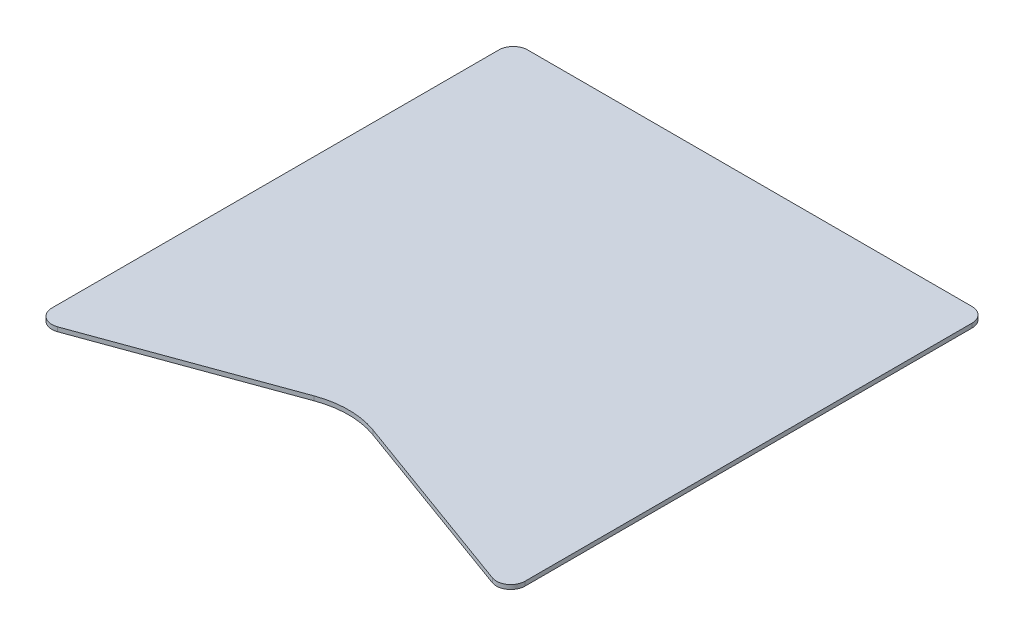
SolidWorks part; units mm, degrees
ref_plane "Front Plane" through (0, 0, 0) normal (0, 0, 1) x (1, 0, 0)
ref_plane "Top Plane" through (0, 0, 0) normal (0, 1, 0) x (1, 0, 0)
ref_plane "Right Plane" through (0, 0, 0) normal (1, 0, 0) x (0, 0, -1)
sketch "Sketch3" plane through (0, 0, 0) normal (0, 1, 0) x (1, 0, 0)
  line L0 (165, 0) -> (998.6493, -303.4235)
  line L1 (0, 0) -> (330, 0)
  line L2 (0, 0) -> (0, 330)
  line L3 (0, 330) -> (330, 330)
  line L4 (330, 0) -> (330, 330)
  line L5 (0, 0) -> (330, 0)
  line L6 (0, 0) -> (0, -60.0551)
  line L7 (0, -60.0551) -> (330, -60.0551)
  line L8 (330, 0) -> (330, -60.0551)
  line L9 (165, 0) -> (-668.6493, -303.4235)
  line L10 (-668.6493, -319.3862) -> (165, -15.9627)
  line L11 (165, -15.9627) -> (998.6493, -319.3862)
  line L12 (-523.6468, -250.6469) -> (0, 0)
  line L13 (-668.6493, -303.4235) -> (0, 16.6298)
  line L14 (15, 0) -> (15, 315)
  line L15 (15, 315) -> (315, 315)
  line L16 (315, 0) -> (315, 315)
  line L17 (0, -25.0551) -> (330, -25.0551)
  line L18 (15, -10.0551) -> (315, -10.0551)
  line L19 (315, -10.0551) -> (315, 0)
  line L20 (15, 0) -> (15, -10.0551)
  line L21 (165, 330) -> (165, 0) construction
  line L22 (998.6493, -303.4235) -> (330, 16.6298)
  line L23 (853.6468, -250.6469) -> (330, 0)
  line L24 (15, 15) -> (315, 15)
  line L25 (-25, 32.3797) -> (15, 32.3797)
  line L26 (-25, 32.3797) -> (-7.7302, -3.7001)
  line L27 (-50, -51.6492) -> (-67.2698, -15.5693)
  line L28 (-50, -51.6492) -> (-36.3192, -89.2369)
  line L29 (165, -79.8133) -> (139.3485, -9.3364)
  line L30 (165, -79.8133) -> (190.6515, -9.3364)
  line L31 (0, 40) -> (15, 40) construction
  line L32 (-23.9741, 5.1545) -> (-17.4979, -8.3755) construction
  line L33 (127.6952, -13.5778) -> (132.8255, -27.6732) construction
  circle A0 centre (-50, -51.6492) radius 40
  circle A1 centre (-50, -51.6492) radius 25
  circle A2 centre (165, -79.8133) radius 75
  circle A3 centre (165, -79.8133) radius 60
  circle A4 centre (380, -51.6492) radius 25
  circle A5 centre (380, -51.6492) radius 40
  circle A6 centre (-25, 32.3797) radius 40
  circle A7 centre (-25, 32.3797) radius 25
  circle A8 centre (355, 32.3797) radius 25
  circle A9 centre (355, 32.3797) radius 40
  dimension "D5" = 150
  dimension "D10" = 80
  dimension "D13" = 80
  dimension "D1" = 330
  dimension "D2" = 330
  dimension "D3" = 15
  dimension "D4" = 15
  dimension "D7" = 15
  dimension "D8" = 35
  dimension "D9" = 70
  dimension "D11" = 50
  dimension "D12" = 15
  dimension "D14" = 290
  dimension "D15" = 48
  dimension "D16" = 180
  dimension "D6" = 15
extrude "Boss-Extrude1" add sketch "Sketch3" along normal blind 3 contours L14 L24 L16 L15 | L16 A9 L4 L3 L2 A6 L14 L15 | L25 A6 L2 | L2 A6 L25 | L26 A6 L2 L13 | L13 A6 L26 | A6 L13 A0 L12 | L12 A0 L27 | L27 A0 L12 | A1 L12 A0 L9 | L9 A0 L28 | L28 A0 L9 | A1 L9 A0 L12 | A0 L9 L6 L12 | A0 L10 L7 L9 | L17 L6 L9 | L20 L1 L6 L17 L9 L18 | A6 L2 L1 L14 | L24 L14 L5 L1 L16 | L5 L20 L18 L9 | A2 L17 L9 L7 L10 | L17 A2 L10 | A2 L18 L9 L17 | L18 A2 L17 L10 L29 | L11 L30 L18 L29 L10 | L29 A2 L18 | L30 A2 L29 L18 | A2 L0 L9 | L18 L19 L1 L0 | A3 L11 L10 | L17 A2 L18 L30 L11 | L11 A2 L17 | A2 L17 L0 L18 | L18 A2 L30 | L19 L18 L0 L17 L8 L5 | A2 L18 L0 | A2 L9 L18 | A6 L12 L2 | A2 L11 L7 L0 L17 | L17 L0 L8 | L11 A5 L0 L7 | L0 A5 L23 L8 | A5 L0 | A5 L23 A4 L0 | A4 | A5 L0 A4 L23 | A5 L23 | L22 A9 L23 A5 | A9 L22 L4 | L4 A9 L16 L5 | L23 A9 L4 | A9 L4 | L22 A8 L4 | A7 L13 L2 | A1 region at (246.673, 0, 4.8576) region at (83.327, 0, 4.8576) region at (165, 0, -7.5) region at (165, 0, 3.8141) region at (191.2006, 0, 9.8141) region at (165, 0, 7.9368) region at (192.103, 0, 9.8735) region at (54.9076, 0, 16.1557) region at (10.3469, 0, -7.7626) region at (319.6531, 0, -7.7626) region at (275.0924, 0, 16.1557) region at (137.897, 0, 9.8735) region at (138.7994, 0, 9.8141) region at (216.3603, 0, 20.7054) region at (165, 0, 15.032) region at (198.1809, 0, 19.4214) region at (-1.8939, 0, 0.5645) region at (-9.3638, 0, 27.8405) region at (165, 0, -165) region at (339.3638, 0, 27.8405) region at (331.8939, 0, 0.5645) region at (113.6397, 0, 20.7054) region at (131.8191, 0, 19.4214) region at (297.9461, 0, 36.7218) region at (266.6993, 0, 44.3391) region at (165, 0, 19.0139) region at (211.7215, 0, 29.7189) region at (-5.7034, 0, -6.5438) region at (6.1083, 0, -20.3096) region at (32.0539, 0, 36.7218) region at (-22.4563, 0, 0.891) region at (-37.5, 0, 9.6347) region at (11.4561, 0, -49.8927) region at (6.1083, 0, -44.4498) region at (323.8917, 0, -32.3797) region at (346.5095, 0, -1.7482) region at (367.5, 0, 9.6347) region at (63.3007, 0, 44.3391) region at (118.2785, 0, 29.7189) region at (326.6299, 0, 68.8353) region at (-3.0031, 0, -18.5218) region at (3.3701, 0, 68.8353) region at (-24.7924, 0, 41.0585) region at (-52.5437, 0, 18.3784) region at (333.0031, 0, -18.5218) region at (393.4309, 0, 23.5896) region at (354.7924, 0, 41.0585) region at (369.3603, 0, 80.8814) region at (-28.0182, 0, 76.7531) region at (-75.8952, 0, 62.5287) region at (-74.318, 0, 28.8009) region at (405.8952, 0, 62.5287) region at (380, 0, 51.6492) region at (-50.7025, 0, 85.0096)
sketch "Sketch5" plane through (0, 0, 0) normal (0, 1, 0) x (1, 0, 0)
  line L0 (0, 58.3508) -> (0, -91.6492)
  line L1 (-90, 58.3508) -> (420, 58.3508) construction
  line L2 (-90, 58.3508) -> (-90, -91.6492) construction
  line L3 (-90, -91.6492) -> (420, -91.6492) construction
  line L4 (420, 58.3508) -> (420, -91.6492) construction
  line L5 (330, 58.3508) -> (420, 58.3508)
  line L6 (420, 58.3508) -> (420, -91.6492)
  line L8 (420, -91.6492) -> (-90, -91.6492)
  line L9 (330, -91.6492) -> (330, 58.3508)
  line L10 (-90, -91.6492) -> (-90, 58.3508)
  line L11 (0, 32.3797) -> (0, 330) construction
  line L14 (330, 32.3797) -> (330, 330) construction
  line L15 (-90, 58.3508) -> (0, 58.3508)
  arc A1 (366.3192, -89.2369) -> (397.2698, -15.5693) centre (380, -51.6492) ccw construction
  arc A2 (-67.2698, -15.5693) -> (-36.3192, -89.2369) centre (-50, -51.6492) ccw construction
  point P8 (0, 0)
  point P9 (0, 0)
  point P19 (0, 0)
  point P21 (0, 0)
  point P22 (0, 0)
  dimension "D1" = 150
extrude "Cut-Extrude3" cut sketch "Sketch5" along normal through all contours L15 L10 L8 L6 L5 L9 L0 | L9 L8 L6 L5 region at (375, 0, 16.6492) region at (-45, 0, 16.6492)
sketch "Sketch6" plane through (0, 3, 0) normal (0, 1, 0) x (1, 0, 0)
  line L0 (330, -76.0178) -> (330, 330) construction
  line L1 (0, 330) -> (330, 330)
  line L2 (0, 330) -> (0, 260)
  line L3 (0, 260) -> (330, 260)
  line L4 (330, 330) -> (330, 260)
  dimension "D1" = 70
extrude "Cut-Extrude4" cut sketch "Sketch6" against normal through all
fillet "Fillet1" radius 10 4 edges at (330, 1.5, 76.0178) (0, 1.5, 76.0178) (330, 1.5, -260) (0, 1.5, -260)
